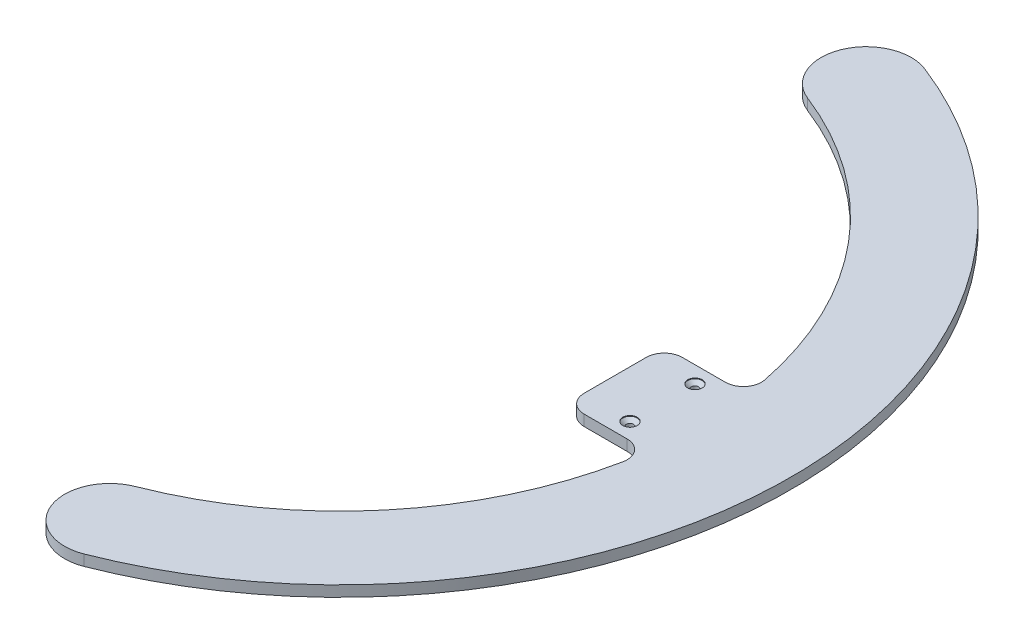
SolidWorks part; units mm, degrees
ref_plane "Front Plane" through (0, 0, 0) normal (0, 0, 1) x (1, 0, 0)
ref_plane "Top Plane" through (0, 0, 0) normal (0, 1, 0) x (1, 0, 0)
ref_plane "Right Plane" through (0, 0, 0) normal (1, 0, 0) x (0, 0, -1)
sketch "Sketch1" plane through (0, 0, 0) normal (0, 1, 0) x (1, 0, 0)
  line L0 (125, 0) -> (-125, 0) construction
  line L1 (0, 0) -> (32.3524, 120.7407)
  line L2 (0, 0) -> (32.3524, -120.7407)
  line L3 (0, 100) -> (0, 125) construction
  line L5 (82.3366, 9) -> (96.3366, 9)
  line L6 (82.3366, 9) -> (82.3366, -9)
  line L7 (82.3366, -9) -> (96.3366, -9)
  line L8 (96.3366, 9) -> (96.3366, -9)
  line L9 (82.3366, 9) -> (96.3366, -9) construction
  line L10 (82.3366, -9) -> (96.3366, 9) construction
  line L11 (93.2366, -10.6) -> (93.2366, -7.4)
  line L12 (93.2366, 10.6) -> (99.4366, 10.6)
  line L13 (93.2366, 10.6) -> (93.2366, 7.4)
  line L14 (93.2366, 7.4) -> (99.4366, 7.4)
  line L15 (99.4366, 10.6) -> (99.4366, 7.4)
  line L16 (93.2366, 10.6) -> (99.4366, 7.4) construction
  line L17 (93.2366, 7.4) -> (99.4366, 10.6) construction
  line L18 (93.2366, -10.6) -> (99.4366, -10.6)
  line L19 (99.4366, -10.6) -> (99.4366, -7.4)
  line L20 (93.2366, -7.4) -> (99.4366, -7.4)
  line L21 (89.3366, 9) -> (89.3366, -9) construction
  line L22 (85.4366, -10.6) -> (85.4366, -7.4)
  line L23 (85.4366, -10.6) -> (79.2366, -10.6)
  line L24 (79.2366, -10.6) -> (79.2366, -7.4)
  line L25 (85.4366, -7.4) -> (79.2366, -7.4)
  line L26 (85.4366, 7.4) -> (79.2366, 7.4)
  line L27 (79.2366, 10.6) -> (79.2366, 7.4)
  line L28 (85.4366, 10.6) -> (79.2366, 10.6)
  line L29 (85.4366, 10.6) -> (85.4366, 7.4)
  line L30 (79.2366, 10.6) -> (76.2366, 10.6) construction
  line L31 (102.4366, 4.4) -> (76.2366, 4.4)
  line L32 (102.4366, 4.4) -> (102.4366, 13.6)
  line L33 (102.4366, 13.6) -> (76.2366, 13.6)
  line L34 (76.2366, 4.4) -> (76.2366, 13.6)
  line L35 (102.4366, 4.4) -> (76.2366, 13.6) construction
  line L36 (102.4366, 13.6) -> (76.2366, 4.4) construction
  line L37 (79.2366, 10.6) -> (79.2366, 13.6) construction
  line L38 (102.4366, -4.4) -> (102.4366, -13.6)
  line L39 (102.4366, -13.6) -> (76.2366, -13.6)
  line L40 (76.2366, -4.4) -> (76.2366, -13.6)
  line L41 (102.4366, -4.4) -> (76.2366, -4.4)
  line L42 (76.2366, -4.4) -> (76.2366, 4.4)
  line L43 (79.2366, 4.4) -> (79.2366, -4.4)
  line L44 (99.4366, 10.6) -> (96.2366, 7.4) construction
  line L45 (99.4366, 9) -> (93.2366, 9) construction
  line L46 (96.3366, 10.6) -> (96.3366, 7.4) construction
  circle A0 centre (0, 0) radius 125
  circle A1 centre (0, 0) radius 100
  circle A2 centre (98.7295, 9.8929) radius 1
  circle A3 centre (98.7295, 8.1071) radius 1
  circle A4 centre (93.9437, 9.8929) radius 1
  circle A5 centre (93.9437, 8.1071) radius 1
  circle A6 centre (84.7295, 8.1071) radius 1
  circle A7 centre (79.9437, 8.1071) radius 1
  circle A8 centre (79.9437, 9.8929) radius 1
  circle A9 centre (84.7295, 9.8929) radius 1
  circle A10 centre (98.7295, -8.1071) radius 1
  circle A11 centre (98.7295, -9.8929) radius 1
  circle A12 centre (93.9437, -8.1071) radius 1
  circle A13 centre (93.9437, -9.8929) radius 1
  circle A14 centre (84.7295, -8.1071) radius 1
  circle A15 centre (84.7295, -9.8929) radius 1
  circle A16 centre (79.9437, -9.8929) radius 1
  circle A17 centre (79.9437, -8.1071) radius 1
  circle A18 centre (89.3366, 9) radius 1
  circle A19 centre (89.3366, -9) radius 1
  point P9 (100, 0)
  point P10 (89.3366, 0)
  dimension "D1" = 250
  dimension "D2" = 25
  dimension "D10" = 2
  dimension "D11" = 2
  dimension "D3" = 75
  dimension "D4" = 6.2
  dimension "D5" = 3.2
  dimension "D6" = 14.8
  dimension "D7" = 7.8
  dimension "D8" = 3
  dimension "D9" = 45
extrude "Boss-Extrude1" add sketch "Sketch1" along normal blind 3 contours A1 L2 A0 L1 | A1 L31 L32 L33 | A1 L39 L38 L41 | L19 A1 L41 L8 L20 | L39 A1 L18 L11 L7 L22 L23 L24 L25 L6 L41 L40 | L43 L31 L42 L41 | L12 A1 L33 L34 L31 L6 L26 L27 L28 L29 L5 L13 | L31 A1 L15 L14 L8 | L31 L8 L14 L13 L5 L29 L26 L6 | L8 L41 L6 L25 L22 L7 L11 L20 | L31 L43 L41 L6 | L41 L8 L31 L6 | L41 A1 L31 L8
fillet "Fillet1" radius 12.5 4 edges at (32.3524, 1.5, 120.7407) (25.8819, 1.5, 96.5926) (32.3524, 1.5, -120.7407) (25.8819, 1.5, -96.5926)
sketch "Sketch2" plane through (0, 3, 0) normal (0, 1, 0) x (1, 0, 0)
  line L3 (93.2366, 9.1858) -> (93.2366, 8.8142)
  line L4 (80.6508, 7.4) -> (84.0224, 7.4)
  line L5 (79.2366, 9.1858) -> (79.2366, 8.8142)
  line L6 (84.0224, 10.6) -> (80.6508, 10.6)
  line L7 (85.4366, 8.8142) -> (85.4366, 9.1858)
  line L8 (80.6508, 7.4) -> (84.0224, 7.4)
  line L9 (79.2366, 9.1858) -> (79.2366, 8.8142)
  line L10 (84.0224, 10.6) -> (80.6508, 10.6)
  line L11 (85.4366, 8.8142) -> (85.4366, 9.1858)
  line L12 (98.0224, 10.6) -> (94.6508, 10.6)
  line L13 (94.6508, 7.4) -> (98.0224, 7.4)
  line L14 (93.2366, 9.1858) -> (93.2366, 8.8142)
  line L15 (98.0224, 10.6) -> (94.6508, 10.6)
  line L16 (94.6508, 7.4) -> (98.0224, 7.4)
  line L17 (93.2366, -8.8142) -> (93.2366, -9.1858)
  line L18 (84.0224, -7.4) -> (80.6508, -7.4)
  line L19 (85.4366, -9.1858) -> (85.4366, -8.8142)
  line L20 (80.6508, -10.6) -> (84.0224, -10.6)
  line L21 (79.2366, -8.8142) -> (79.2366, -9.1858)
  line L22 (84.0224, -7.4) -> (80.6508, -7.4)
  line L23 (85.4366, -9.1858) -> (85.4366, -8.8142)
  line L24 (80.6508, -10.6) -> (84.0224, -10.6)
  line L25 (79.2366, -8.8142) -> (79.2366, -9.1858)
  line L26 (98.0224, -7.4) -> (94.6508, -7.4)
  line L27 (94.6508, -10.6) -> (98.0224, -10.6)
  line L28 (93.2366, -8.8142) -> (93.2366, -9.1858)
  line L29 (98.0224, -7.4) -> (94.6508, -7.4)
  line L30 (94.6508, -10.6) -> (98.0224, -10.6)
  arc A4 (84.0224, 7.4) -> (85.4366, 8.8142) centre (84.7295, 8.1071) ccw
  arc A5 (79.2366, 8.8142) -> (80.6508, 7.4) centre (79.9437, 8.1071) ccw
  arc A6 (80.6508, 10.6) -> (79.2366, 9.1858) centre (79.9437, 9.8929) ccw
  arc A7 (85.4366, 9.1858) -> (84.0224, 10.6) centre (84.7295, 9.8929) ccw
  arc A8 (84.0224, 7.4) -> (85.4366, 8.8142) centre (84.7295, 8.1071) ccw
  arc A9 (79.2366, 8.8142) -> (80.6508, 7.4) centre (79.9437, 8.1071) ccw
  arc A10 (80.6508, 10.6) -> (79.2366, 9.1858) centre (79.9437, 9.8929) ccw
  arc A11 (85.4366, 9.1858) -> (84.0224, 10.6) centre (84.7295, 9.8929) ccw
  arc A13 (93.2366, 8.8142) -> (94.6508, 7.4) centre (93.9437, 8.1071) ccw
  arc A14 (94.6508, 10.6) -> (93.2366, 9.1858) centre (93.9437, 9.8929) ccw
  arc A15 (99.5629, 9.3401) -> (98.0224, 10.6) centre (98.7295, 9.8929) ccw
  arc A16 (99.6355, 8.5304) -> (99.5629, 9.3401) centre (0, 0) ccw
  arc A17 (98.0224, 7.4) -> (99.6355, 8.5304) centre (98.7295, 8.1071) ccw
  arc A18 (93.2366, 8.8142) -> (94.6508, 7.4) centre (93.9437, 8.1071) ccw
  arc A19 (94.6508, 10.6) -> (93.2366, 9.1858) centre (93.9437, 9.8929) ccw
  arc A20 (99.5629, 9.3401) -> (98.0224, 10.6) centre (98.7295, 9.8929) ccw
  arc A21 (99.6355, 8.5304) -> (99.5629, 9.3401) centre (0, 0) ccw
  arc A22 (98.0224, 7.4) -> (99.6355, 8.5304) centre (98.7295, 8.1071) ccw
  arc A23 (85.4366, -8.8142) -> (84.0224, -7.4) centre (84.7295, -8.1071) ccw
  arc A24 (84.0224, -10.6) -> (85.4366, -9.1858) centre (84.7295, -9.8929) ccw
  arc A25 (79.2366, -9.1858) -> (80.6508, -10.6) centre (79.9437, -9.8929) ccw
  arc A26 (80.6508, -7.4) -> (79.2366, -8.8142) centre (79.9437, -8.1071) ccw
  arc A27 (85.4366, -8.8142) -> (84.0224, -7.4) centre (84.7295, -8.1071) ccw
  arc A28 (84.0224, -10.6) -> (85.4366, -9.1858) centre (84.7295, -9.8929) ccw
  arc A29 (79.2366, -9.1858) -> (80.6508, -10.6) centre (79.9437, -9.8929) ccw
  arc A30 (80.6508, -7.4) -> (79.2366, -8.8142) centre (79.9437, -8.1071) ccw
  arc A32 (94.6508, -7.4) -> (93.2366, -8.8142) centre (93.9437, -8.1071) ccw
  arc A33 (99.6355, -8.5304) -> (98.0224, -7.4) centre (98.7295, -8.1071) ccw
  arc A34 (99.5629, -9.3401) -> (99.6355, -8.5304) centre (0, 0) ccw
  arc A35 (98.0224, -10.6) -> (99.5629, -9.3401) centre (98.7295, -9.8929) ccw
  arc A36 (93.2366, -9.1858) -> (94.6508, -10.6) centre (93.9437, -9.8929) ccw
  arc A37 (94.6508, -7.4) -> (93.2366, -8.8142) centre (93.9437, -8.1071) ccw
  arc A38 (99.6355, -8.5304) -> (98.0224, -7.4) centre (98.7295, -8.1071) ccw
  arc A39 (99.5629, -9.3401) -> (99.6355, -8.5304) centre (0, 0) ccw
  arc A40 (98.0224, -10.6) -> (99.5629, -9.3401) centre (98.7295, -9.8929) ccw
  arc A41 (93.2366, -9.1858) -> (94.6508, -10.6) centre (93.9437, -9.8929) ccw
  dimension "D1" = 0
  dimension "D2" = 0
  dimension "D3" = 0
  dimension "D4" = 0
extrude "Boss-Extrude2" add sketch "Sketch2" against normal offset from surface (1.6 mm away) 1.4 up to face at (96.3311, 0, -8.9863)
hole_wizard "CSK for M2 Flat Head Machine Screw1" positions "Sketch3" profile "Sketch4" countersink size "M2" standard "ANSI Metric" end condition through all
sketch "Sketch3" plane through (0, 3, 0) normal (0, 1, 0) x (1, 0, 0)
  point P0 (89.3366, 9)
  point P3 (89.3366, -9)
sketch "Sketch4" plane through (89.3366, 3, -9) normal (1, 0, 0) x (0, 0, 1)
  line L0 (0, 0) -> (0, 3)
  line L1 (0, 3) -> (1, 3)
  line L2 (1, 3) -> (1, 1.2)
  line L3 (1, 1.2) -> (2, 0.2)
  line L4 (2, 0.2) -> (2, 0)
  line L6 (2, 0) -> (0, 0)
  line L7 (-1, 1.2) -> (-2, 0.2) construction
  line L11 (0, -6.35) -> (0, 107.95) construction
  dimension "Thru Hole Dia." = 2
  dimension "Thru Hole Depth" = 3
  dimension "C'Sink Dia." = 4
  dimension "C'Sink Angle" = 90
  dimension "Head Clearance" = 0.2
fillet "Fillet2" radius 5 4 edges at (76.2366, 1.5, -13.6) (76.2366, 1.5, 13.6) (99.0709, 1.5, 13.6) (99.0709, 1.5, -13.6)
